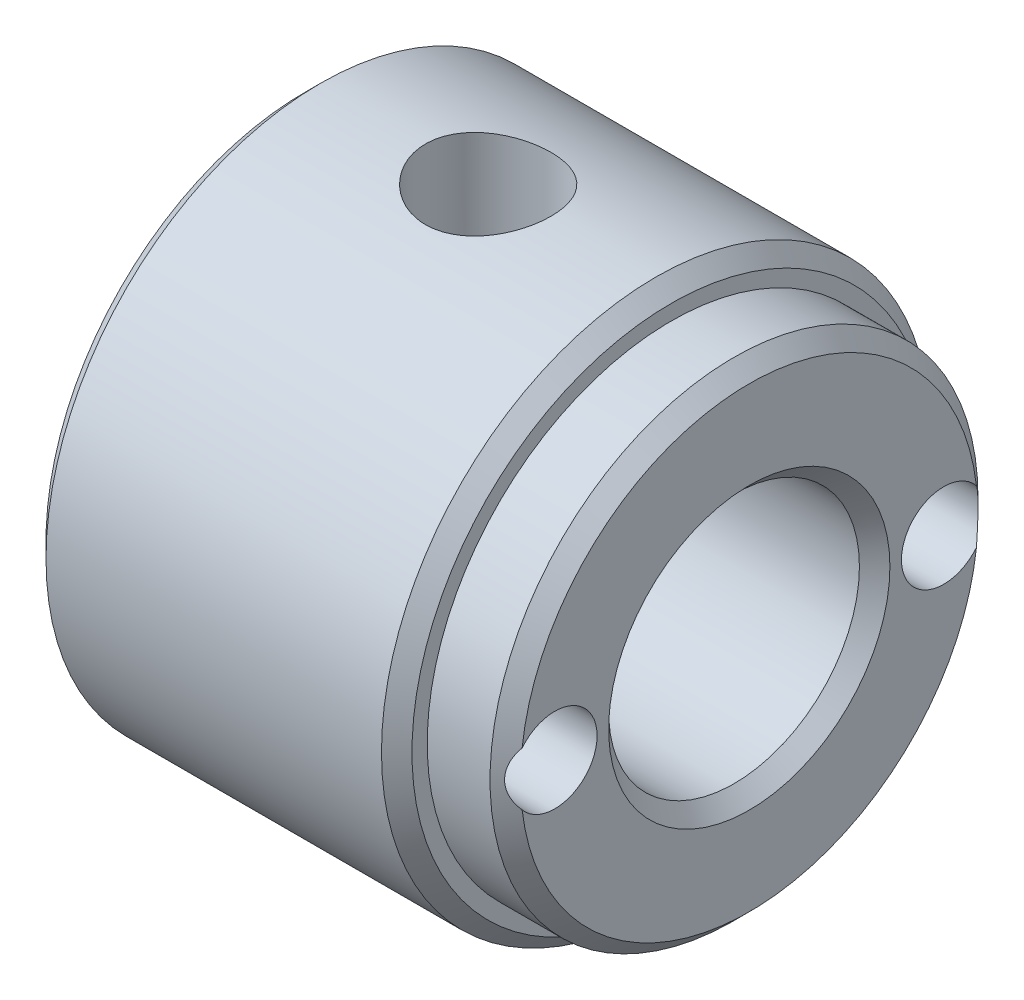
SolidWorks part; units mm, degrees
ref_plane "Front Plane" through (0, 0, 0) normal (0, 0, 1) x (1, 0, 0)
ref_plane "Top Plane" through (0, 0, 0) normal (0, 1, 0) x (1, 0, 0)
ref_plane "Right Plane" through (0, 0, 0) normal (1, 0, 0) x (0, 0, -1)
sketch "Sketch1" plane through (0, 0, 0) normal (1, 0, 0) x (0, 0, -1)
  line L0 (0, 0) -> (0, 0.7417) construction
  line L1 (-3.2639, 0) -> (-6.35, 0) construction
  circle A0 centre (0, 0) radius 6.35
  circle A1 centre (0, 0) radius 6.35
  circle A2 centre (0, 0) radius 3.2639
  circle A3 centre (-5.061, 0) radius 1.1
  circle A5 centre (0, 0) radius 7.1438
  circle A6 centre (5.061, 0) radius 1.1
  point P11 (0, 0)
  point P15 (-5.061, 1.4951)
  dimension "D1" = 12.7
  dimension "D2" = 6.5278
  dimension "D3" = 2.2
  dimension "D4" = 14.2875
  dimension "D5" = 10.1219
extrude "Inner Side Extrude" add sketch "Sketch1" along normal blind 2.032 contours A0 A2 A3 A6 region at (0, 0, 6.1704)
extrude "Outer Side Extrude" add sketch "Sketch1<3>" against normal blind 9.525 contours A0 A2 A3 A6 | A5 A0 region at (0, 0, 6.1704) region at (0, 0, 6.9417)
sketch "Sketch1<3>" plane through (0, 0, 0) normal (1, 0, 0) x (0, 0, -1) same geometry as "Sketch1"
sketch "Sketch2" plane through (0, 0, 0) normal (0, 1, 0) x (1, 0, 0)
  line L0 (-9.525, 7.1438) -> (-9.525, -7.1438) construction
  line L1 (-9.525, 0) -> (0, 0) construction
  circle A0 centre (-4.7625, 0) radius 1.632
  point P0 (-9.525, 0)
  dimension "D1" = 3.2639
extrude "Clevis Pin Cut" cut sketch "Sketch2" against normal through all and the other way through all
chamfer "Chamfer so Steve Doesn't cut himself" distance 0.3969 angle 45 5 edges at (-9.525, 0, -3.2639) (2.032, 0, -3.2639) (2.032, 0, -6.35) (-9.525, 0, -7.1438) (0, 0, -7.1438)
